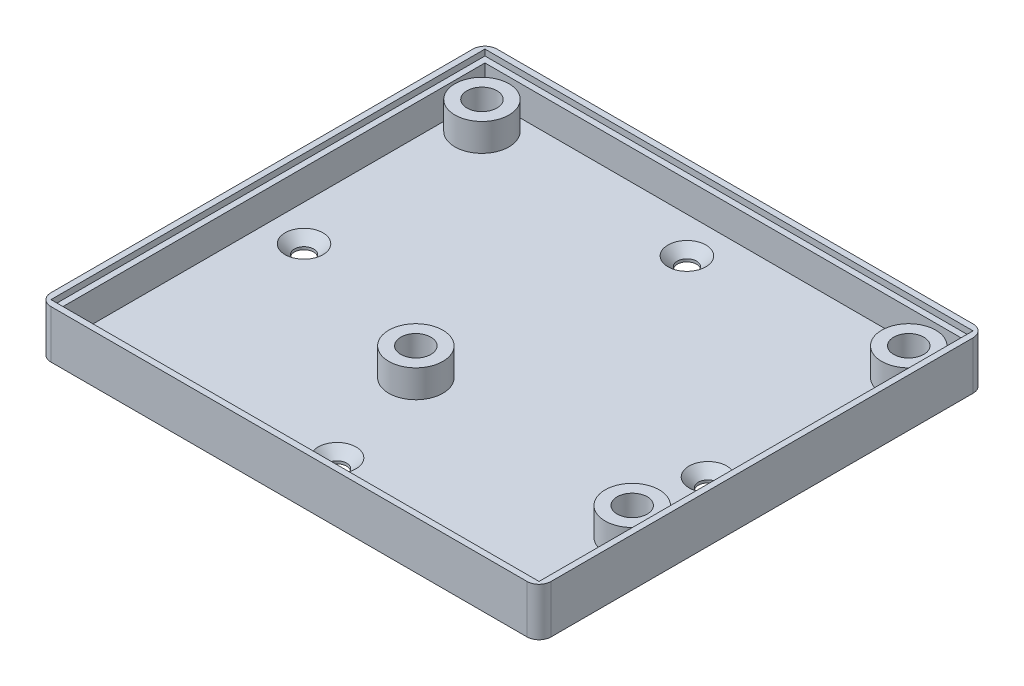
SolidWorks part; units mm, degrees
ref_plane "Front Plane" through (0, 0, 0) normal (0, 0, 1) x (1, 0, 0)
ref_plane "Top Plane" through (0, 0, 0) normal (0, 1, 0) x (1, 0, 0)
ref_plane "Right Plane" through (0, 0, 0) normal (1, 0, 0) x (0, 0, -1)
sketch "Sketch1" plane through (0, 0, 0) normal (0, 1, 0) x (1, 0, 0)
  line L1 (0, 0) -> (83.2, 0)
  line L2 (0, 0) -> (0, 74.2)
  line L3 (0, 74.2) -> (83.2, 74.2)
  line L4 (83.2, 0) -> (83.2, 74.2)
  dimension "D1" = 83.2
  dimension "D2" = 74.2
extrude "Boss-Extrude1" add sketch "Sketch1" along normal blind 8
shell "Shell1" thickness 2 removed face at (41.6, 8, -37.1)
sketch "Sketch2" plane through (0, 2, 0) normal (0, 1, 0) x (1, 0, 0)
  line L2 (2, 72.2) -> (2, 2) construction
  line L3 (81.2, 72.2) -> (2, 72.2) construction
  line L4 (2, 2) -> (81.2, 2) construction
  line L5 (81.2, 2) -> (81.2, 72.2) construction
  circle A0 centre (6.6, 67.1) radius 2.5
  circle A1 centre (6.6, 67.1) radius 4.5
  circle A2 centre (36.6, 26.1) radius 2.5
  circle A3 centre (36.6, 26.1) radius 4.5
  circle A4 centre (77.6, 67.1) radius 2.5
  circle A5 centre (77.6, 67.1) radius 4.5
  circle A6 centre (77.6, 21.1) radius 2.5
  circle A7 centre (77.6, 21.1) radius 4.5
  dimension "D1" = 4.6
  dimension "D3" = 5
  dimension "D4" = 9
  dimension "D5" = 5
  dimension "D6" = 34.6
  dimension "D7" = 24.1
  dimension "D8" = 9
  dimension "D9" = 3.6
  dimension "D10" = 5.1
  dimension "D11" = 5
  dimension "D12" = 9
  dimension "D13" = 3.6
  dimension "D15" = 5
  dimension "D16" = 9
  dimension "D2" = 5.1
  dimension "D14" = 19.1
extrude "Boss-Extrude2" add sketch "Sketch2" along normal offset from surface (4.6 mm away) 1.4 up to face at (41.6, 8, -37.1)
sketch "Sketch3" plane through (0, 8, 0) normal (0, 1, 0) x (1, 0, 0)
  line L7 (1, 73.2) -> (1, 1)
  line L8 (1, 1) -> (82.2, 1)
  line L9 (82.2, 1) -> (82.2, 73.2)
  line L10 (82.2, 73.2) -> (1, 73.2)
  line L11 (0, 74.2) -> (0, 0)
  line L12 (0, 0) -> (83.2, 0)
  line L13 (83.2, 0) -> (83.2, 74.2)
  line L14 (83.2, 74.2) -> (0, 74.2)
  line L15 (0, 74.2) -> (0, 0) construction
  line L16 (0, 0) -> (83.2, 0) construction
  line L17 (83.2, 0) -> (83.2, 74.2) construction
  line L18 (83.2, 74.2) -> (0, 74.2) construction
  dimension "D1" = 0
  dimension "D2" = 1
extrude "Cut-Extrude1" cut sketch "Sketch3" against normal blind 1
sketch "Sketch4" plane through (0, 2, 0) normal (0, 1, 0) x (1, 0, 0)
  circle A1 centre (6.6, 67.1) radius 2.5
  circle A2 centre (6.6, 67.1) radius 2.5
  circle A3 centre (77.6, 67.1) radius 2.5
  circle A4 centre (77.6, 67.1) radius 2.5
  circle A5 centre (36.6, 26.1) radius 2.5
  circle A6 centre (36.6, 26.1) radius 2.5
  circle A7 centre (77.6, 21.1) radius 2.5
  circle A8 centre (77.6, 21.1) radius 2.5
  dimension "D1" = 0
  dimension "D2" = 0
  dimension "D3" = 0
  dimension "D4" = 0
hole_wizard "CSK for M3 Flat Head Machine Screw1" positions "Sketch5" profile "Sketch6" countersink size "M3" standard "ANSI Metric" end condition through all
sketch "Sketch5" plane through (0, 2, 0) normal (0, 1, 0) x (1, 0, 0)
  line L0 (0, 74.2) -> (0, 0) construction
  line L1 (0, 0) -> (83.2, 0) construction
  line L2 (81.2, 72.2) -> (2, 72.2) construction
  line L3 (83.2, 0) -> (83.2, 74.2) construction
  line L4 (83.2, 74.2) -> (0, 74.2) construction
  point P0 (41.6, 66.2)
  point P2 (8, 36.1)
  point P4 (75.2, 36.1)
  point P6 (41.6, 8)
  dimension "D1" = 8
  dimension "D2" = 36.1
  dimension "D3" = 36.1
  dimension "D4" = 36.1
  dimension "D5" = 8
  dimension "D6" = 8
  dimension "D7" = 8
  dimension "D8" = 41.6
  dimension "D9" = 41.6
  dimension "D10" = 41.6
sketch "Sketch6" plane through (41.6, 2, -66.2) normal (1, 0, 0) x (0, 0, 1)
  line L0 (0, 0) -> (0, 2)
  line L1 (0, 2) -> (1.6, 2)
  line L2 (1.6, 2) -> (1.6, 1.55)
  line L3 (1.6, 1.55) -> (3.15, 0)
  line L5 (3.15, 0) -> (0, 0)
  line L6 (-1.6, 1.55) -> (-3.15, 0) construction
  line L11 (0, -6.35) -> (0, 107.95) construction
  dimension "Thru Hole Dia." = 3.2
  dimension "Thru Hole Depth" = 2
  dimension "Near C'Sink Dia." = 6.3
  dimension "Near C'Sink Angle" = 90
fillet "Fillet1" radius 2 4 edges at (0, 4, -74.2) (83.2, 4, -74.2) (83.2, 4, 0) (0, 4, 0)
extrude "Cut-Extrude2" cut sketch "Sketch4" against normal blind 0.5
